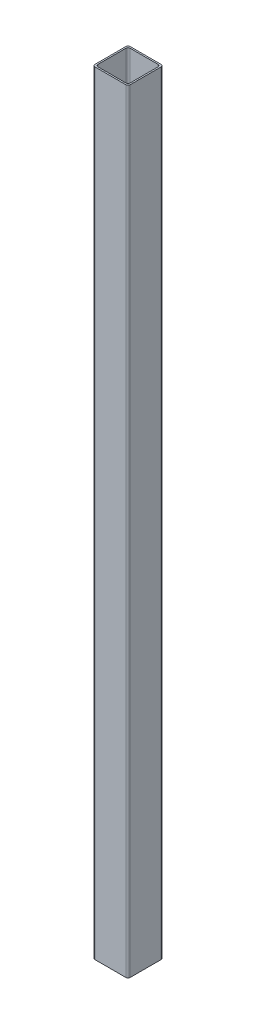
SolidWorks part; units mm, degrees
material "Brass"
ref_plane "Front Plane" through (0, 0, 0) normal (0, 0, 1) x (1, 0, 0)
ref_plane "Top Plane" through (0, 0, 0) normal (0, 1, 0) x (1, 0, 0)
ref_plane "Right Plane" through (0, 0, 0) normal (1, 0, 0) x (0, 0, -1)
sketch "Sketch1" plane through (0, 0, 0) normal (0, 1, 0) x (1, 0, 0)
  line L1 (-1.625, -1.875) -> (1.625, -1.875)
  line L2 (-1.875, -1.625) -> (-1.875, 1.625)
  line L3 (-1.625, 1.875) -> (1.625, 1.875)
  line L4 (1.875, -1.625) -> (1.875, 1.625)
  line L5 (-1.875, -1.875) -> (1.875, 1.875) construction
  line L6 (-1.875, 1.875) -> (1.875, -1.875) construction
  line L7 (-1.8, -2.05) -> (1.8, -2.05)
  line L8 (-2.05, -1.8) -> (-2.05, 1.8)
  line L9 (-1.8, 2.05) -> (1.8, 2.05)
  line L10 (2.05, -1.8) -> (2.05, 1.8)
  line L11 (-2.05, -2.05) -> (2.05, 2.05) construction
  line L12 (-2.05, 2.05) -> (2.05, -2.05) construction
  arc A0 (-1.8, -2.05) -> (-2.05, -1.8) centre (-1.8, -1.8) cw
  arc A1 (-2.05, 1.8) -> (-1.8, 2.05) centre (-1.8, 1.8) cw
  arc A2 (1.8, 2.05) -> (2.05, 1.8) centre (1.8, 1.8) cw
  arc A3 (1.8, -2.05) -> (2.05, -1.8) centre (1.8, -1.8) ccw
  arc A4 (1.625, -1.875) -> (1.875, -1.625) centre (1.625, -1.625) ccw
  arc A5 (1.625, 1.875) -> (1.875, 1.625) centre (1.625, 1.625) cw
  arc A6 (-1.875, 1.625) -> (-1.625, 1.875) centre (-1.625, 1.625) cw
  arc A7 (-1.625, -1.875) -> (-1.875, -1.625) centre (-1.625, -1.625) cw
  point P0 (0, 0)
  point P6 (0, 0)
  point P11 (0, 0)
  point P12 (0, 0)
  point P13 (0, 0)
  point P14 (0, 0)
  dimension "D3" = 0.25
  dimension "D1" = 4.1
  dimension "D2" = 3.75
extrude "Boss-Extrude1" add sketch "Sketch1" along normal blind 90
